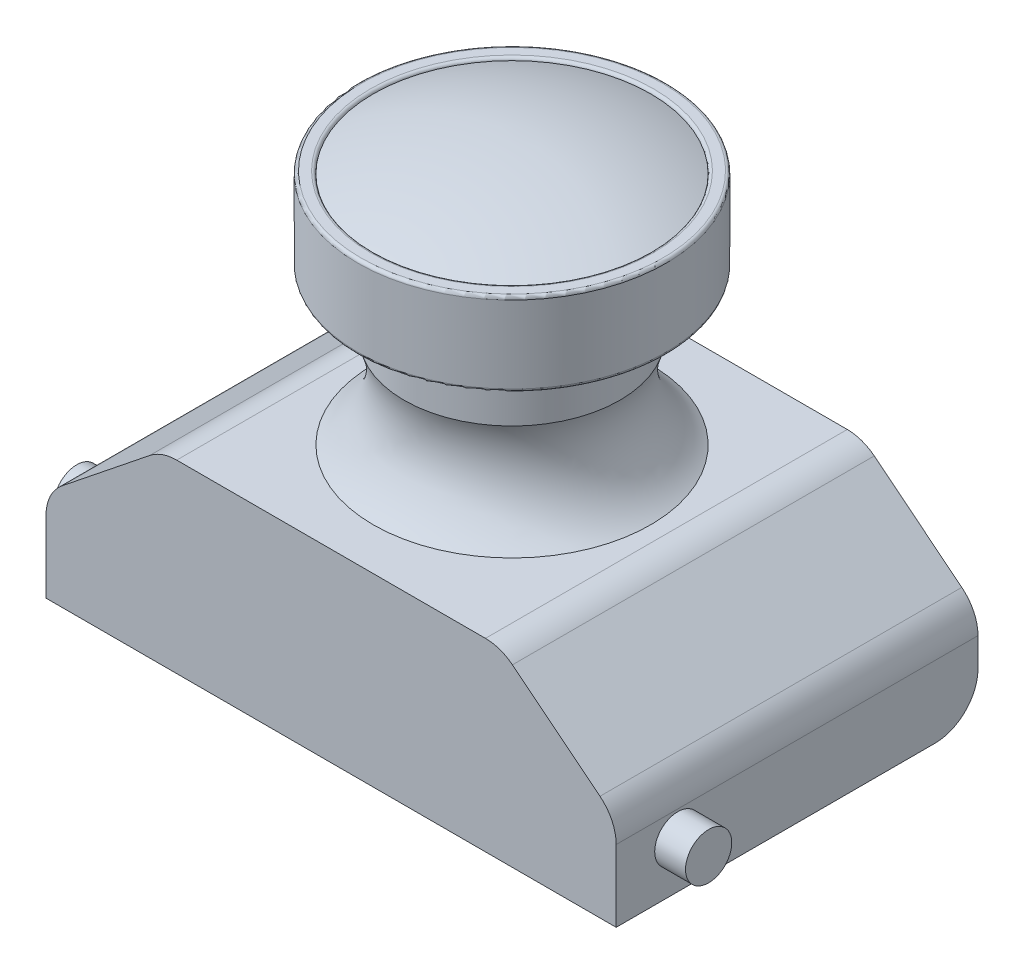
SolidWorks part; units mm, degrees
ref_plane "Front Plane" through (0, 0, 0) normal (0, 0, 1) x (1, 0, 0)
ref_plane "Top Plane" through (0, 0, 0) normal (0, 1, 0) x (1, 0, 0)
ref_plane "Right Plane" through (0, 0, 0) normal (1, 0, 0) x (0, 0, -1)
sketch "Sketch1" plane through (0, 0, 0) normal (0, 0, 1) x (1, 0, 0)
  line L0 (-9.25, 0) -> (9.25, 0)
  line L1 (9.25, 0) -> (9.25, 3)
  line L2 (9.25, 3) -> (5.5, 6)
  line L3 (5.5, 6) -> (-5.5, 6)
  line L4 (-5.5, 6) -> (-9.25, 3)
  line L5 (-9.25, 3) -> (-9.25, 0)
  point P4 (0, 0)
  point P8 (0, 6)
  point P9 (0, 0)
  point P10 (0, 0)
  point P12 (7.7288, 4.8171)
  dimension "D1" = 3
  dimension "D2" = 18.5
  dimension "D3" = 11
  dimension "D4" = 3
extrude "Boss-Extrude1" add sketch "Sketch1" along normal mid plane 11.74
ref_plane "Plane1" through (0, 0, 0) normal (0, 0, 1) x (1, 0, 0)
sketch "Sketch2" plane through (0, 0, 0) normal (0, 0, 1) x (1, 0, 0)
  line L1 (5.5, 6) -> (-5.5, 6) construction
  line L2 (0, 13.5) -> (4.5, 13.5)
  line L3 (4.5, 13.5) -> (4.5, 13.7)
  line L9 (5, 11) -> (3.5, 11)
  line L11 (3.5, 11) -> (3.5, 9)
  line L12 (4.5, 6) -> (0, 6)
  line L13 (5, 11) -> (5, 13.7)
  line L14 (4.5, 13.7) -> (5, 13.7)
  line L15 (6.6643, 15.6088) -> (6.6848, 15.6088)
  line L16 (0, 13.5) -> (0, 6)
  arc A3 (3.5, 9) -> (4.5, 6) centre (5.8371, 8.1124) ccw
  point P12 (0, 6)
  dimension "D1" = 7.5
  dimension "D7" = 3
  dimension "D2" = 2
  dimension "D8" = 2.5
  dimension "D3" = 0.5
  dimension "D4" = 0.2
  dimension "D5" = 5
  dimension "D6" = 1.5
  dimension "D10" = 4.5
revolve "Revolve5" add sketch "Sketch2" angle 360 about L16 region at (2.0898, 10.0285, 0)
sketch "Sketch3" plane through (0, 0, 0) normal (0, 0, 1) x (1, 0, 0)
  line L0 (0, 20.2981) -> (0, 0) construction
  line L1 (0, 13.5) -> (0, 14.5418)
  line L2 (4.75, 13.5) -> (0, 13.5)
  line L3 (4.5, 13.7) -> (-4.5, 13.7) construction
  arc A0 (0, 14.5418) -> (4.75, 13.5) centre (0, 3.1918) cw
  point P7 (0, 13.4114)
  dimension "D1" = 4.75
  dimension "D2" = 11.35
  dimension "D3" = 0.2
revolve "Revolve6" add sketch "Sketch3" angle 360 about L0
ref_plane "Plane2" through (0, 0, 0) normal (-1, 0, 0) x (0, 0, 1)
sketch "Sketch6" plane through (0, 0, 0) normal (-1, 0, 0) x (0, 0, 1)
  line L0 (5.87, 3) -> (5.87, 0) construction
  line L1 (5.87, 0) -> (-5.87, 0) construction
  circle A0 centre (3.87, 1.5) radius 0.75
  dimension "D1" = 1.5
  dimension "D2" = 2
  dimension "D3" = 1.5
extrude "Boss-Extrude2" add sketch "Sketch6" along normal mid plane 20.5
fillet "Fillet1" radius 0.1 3 edges at (0, 13.7, 4.5) (0, 13.7, 5) (0, 11, 5)
fillet "Fillet2" radius 1.4 4 edges at (0, 0, -5.87) (9.25, 3, 0) (-9.25, 3, 0) (-5.5, 6, 0)
fillet "Fillet3" radius 1.4 1 edges at (5.5, 6, 0)
